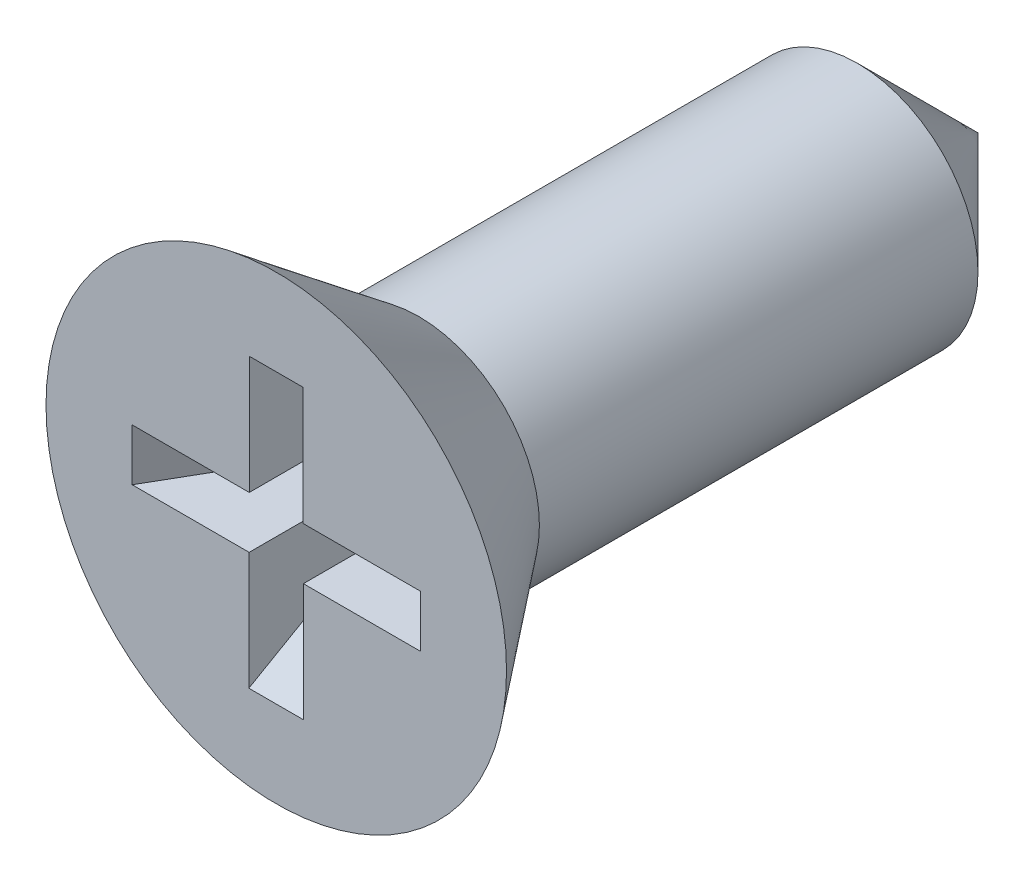
SolidWorks part; units mm, degrees
ref_plane "Plan de face" through (0, 0, 0) normal (0, 0, 1) x (1, 0, 0)
ref_plane "Plan de dessus" through (0, 0, 0) normal (0, 1, 0) x (1, 0, 0)
ref_plane "Plan de droite" through (0, 0, 0) normal (1, 0, 0) x (0, 0, -1)
sketch "Esquisse1" plane through (0, 0, 0) normal (1, 0, 0) x (0, 0, -1)
  line L0 (-1.6035, 0) -> (7.1529, 0) construction
  line L1 (0, 5.0438) -> (0, -4.594) construction
  line L2 (0, 2.1) -> (1.3, 1.1)
  line L3 (1.3, 1.1) -> (1.3, 0)
  line L4 (-1.442, 2.1) -> (2.7621, 2.1) construction
  line L5 (0, 2.1) -> (8.841, -4.7008) construction
  line L6 (-1.0988, 1.1) -> (4.1029, 1.1) construction
  line L7 (1.3, 0) -> (0, 0)
  line L9 (0, 2.1) -> (0, 0)
  dimension "D1" = 1.1
revolve "Révolution2" add sketch "Esquisse1" angle 360 about L0
sketch "Esquisse3" plane through (0, 0, 0) normal (0, 0, 1) x (1, 0, 0)
  circle A0 centre (0, 0) radius 1.1
extrude "Extrusion1" add sketch "Esquisse3" against normal blind 6.4
sketch "Esquisse2" plane through (0, 0, 0) normal (0, 0, 1) x (1, 0, 0)
  line L0 (0.2472, -0.2369) -> (1.3138, -0.2373)
  line L1 (0.246, 0.2369) -> (1.3138, 0.2373)
  line L2 (-1.314, -0.2365) -> (-0.2472, -0.2368)
  line L3 (-0.2433, 1.3127) -> (-0.246, 0.2368)
  line L4 (-1.314, 0.2365) -> (-0.246, 0.2368)
  line L5 (0.2433, 1.3127) -> (0.246, 0.2369)
  line L6 (-0.2433, 1.3127) -> (0.2433, 1.3127)
  line L7 (1.3138, 0.2373) -> (1.3138, -0.2373)
  line L8 (0.25, -1.3115) -> (-0.25, -1.3115)
  line L9 (-1.314, -0.2365) -> (-1.314, 0.2365)
  line L10 (-0.2472, -0.2368) -> (-0.25, -1.3115)
  line L12 (0.2472, -0.2369) -> (0.25, -1.3115)
  circle A0 centre (0, 0) radius 1.3351 construction
extrude "Enlèv. mat.-Extru.2" cut sketch "Esquisse2" against normal blind 1
draft "Dépouille1" type of draft neutral plane draft angle 30 faces to draft 4 face at (0.0042, 1.3127, -0.6648) face at (1.3138, -0.0043, -0.6648) face at (-0.004, -1.3115, -0.6648) face at (-1.314, 0.0043, -0.6648) neutral plane through (0, 2.1, 0) neutral plane normal (0, 0, 1) parameters "D1"=30
chamfer "Chanfrein1" distance 1.1 angle 45 1 edges at (1.1, 0, -6.4)
